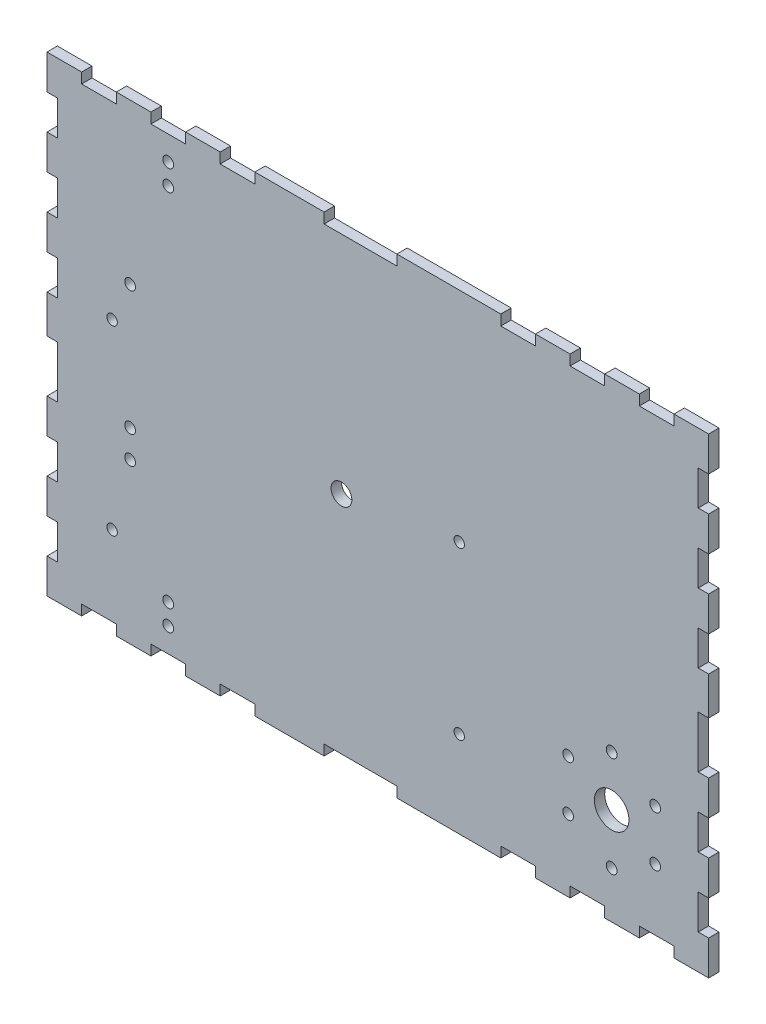
SolidWorks part; units mm, degrees
ref_plane "Front Plane" through (0, 0, 0) normal (0, 0, 1) x (1, 0, 0)
ref_plane "Top Plane" through (0, 0, 0) normal (0, 1, 0) x (1, 0, 0)
ref_plane "Right Plane" through (0, 0, 0) normal (1, 0, 0) x (0, 0, -1)
sketch "Sketch2" plane through (0, 0, 0) normal (0, 0, 1) x (1, 0, 0)
  line L1 (0, 0) -> (191, 0)
  line L2 (0, 0) -> (0, 136)
  line L3 (0, 136) -> (191, 136)
  line L4 (191, 0) -> (191, 136)
  circle A0 centre (35, 16) radius 1.55 construction
  circle A1 centre (35, 10) radius 1.55 construction
  circle A2 centre (24, 46.0692) radius 1.55 construction
  circle A3 centre (24, 54.0692) radius 1.55 construction
  circle A5 centre (24, 89.9308) radius 1.55 construction
  circle A6 centre (35, 120) radius 1.55 construction
  circle A7 centre (35, 126) radius 1.55 construction
  circle A8 centre (175.5574, 35.25) radius 1.55 construction
  circle A9 centre (163, 42.5) radius 1.55 construction
  circle A10 centre (150.4426, 35.25) radius 1.55 construction
  circle A11 centre (150.4426, 20.75) radius 1.55 construction
  circle A12 centre (163, 13.5) radius 1.55 construction
  circle A13 centre (175.5574, 20.75) radius 1.55 construction
  circle A14 centre (35, 16) radius 1.55
  circle A15 centre (35, 10) radius 1.55
  circle A16 centre (24, 46.0692) radius 1.55
  circle A17 centre (24, 54.0692) radius 1.55
  circle A18 centre (18.8, 26) radius 1.5 construction
  circle A19 centre (24, 89.9308) radius 1.55
  circle A20 centre (35, 120) radius 1.55
  circle A21 centre (35, 126) radius 1.55
  circle A22 centre (175.5574, 35.25) radius 1.55
  circle A23 centre (163, 42.5) radius 1.55
  circle A24 centre (150.4426, 35.25) radius 1.55
  circle A25 centre (150.4426, 20.75) radius 1.55
  circle A26 centre (163, 13.5) radius 1.55
  circle A27 centre (175.5574, 20.75) radius 1.55
  circle A28 centre (18.8, 78.5) radius 1.5 construction
  circle A29 centre (18.8, 78.5) radius 1.5
  circle A30 centre (119, 73) radius 1.5 construction
  circle A31 centre (119, 25) radius 1.5 construction
  circle A32 centre (18.8, 26) radius 1.5
  circle A33 centre (119, 73) radius 1.5
  circle A34 centre (119, 25) radius 1.5
extrude "Boss-Extrude1" add sketch "Sketch2" along normal blind 3
ref_axis "Axis1" through (0, 68, 3) along (1, 0, 0)
ref_plane "Plane1" through (0, 68, 0) normal (0, 1, 0) x (1, 0, 0)
ref_axis "Axis2" through (95.5, 0, 3) along (0, 1, 0)
ref_plane "Plane2" through (95.5, 0, 0) normal (1, 0, 0) x (0, 0, -1)
sketch "Sketch3" plane through (0, 0, 3) normal (0, 0, 1) x (1, 0, 0)
  line L0 (0, 3) -> (191, 3) construction
  line L1 (0, 136) -> (0, 0) construction
  line L2 (191, 0) -> (191, 136) construction
  line L3 (0, 0) -> (191, 0) construction
  line L4 (10, 0) -> (10, 3)
  line L5 (20, 0) -> (20, 3)
  line L6 (30, 0) -> (30, 3)
  line L7 (40, 0) -> (40, 3)
  line L8 (50, 0) -> (50, 3)
  line L9 (60, 0) -> (60, 3)
  line L10 (10, 0) -> (20, 0)
  line L11 (20, 3) -> (10, 3)
  line L12 (30, 0) -> (40, 0)
  line L13 (40, 3) -> (30, 3)
  line L14 (50, 0) -> (60, 0)
  line L15 (80, 3) -> (80, 0)
  line L16 (60, 3) -> (50, 3)
  line L17 (181, 0) -> (181, 3)
  line L18 (171, 0) -> (171, 3)
  line L19 (161, 0) -> (161, 3)
  line L20 (151, 0) -> (151, 3)
  line L21 (141, 0) -> (141, 3)
  line L22 (131, 0) -> (131, 3)
  line L23 (181, 0) -> (171, 0)
  line L24 (171, 0) -> (170.9794, -0.0476)
  line L25 (171, 3) -> (181, 3)
  line L26 (181, 3) -> (181.0353, 3.2173)
  line L27 (161, 0) -> (151, 0)
  line L28 (161, 3) -> (151, 3)
  line L29 (141, 0) -> (131, 0)
  line L30 (131, 3) -> (141, 3)
  line L31 (141, 3) -> (140.9859, 2.9583)
  line L32 (101, 0) -> (101, 3)
  line L33 (80, 0) -> (101, 0)
  line L34 (101, 3) -> (80, 3)
  line M15 (0, 0) -> (191, 0)
  dimension "D6" = 20
  dimension "D1" = 3
  dimension "D2" = 10
  dimension "D4" = 10
  dimension "D7" = 30
  dimension "D3" = 6
  dimension "D5" = 6
extrude "Cut-Extrude1" cut sketch "Sketch3" against normal up to next contours L5 L11 L4 M15 | L7 L13 L6 M15 | L9 L16 L8 M15 | L32 L34 L15 M15 | L30 L22 L21 M15 | L19 L28 L20 M15 | L25 L18 L17 M15 region at (176, 1.5, 3) region at (156, 1.5, 3) region at (136, 1.5, 3) region at (90.5, 1.5, 3) region at (55, 1.5, 3) region at (35, 1.5, 3) region at (15, 1.5, 3)
mirror "Mirror1" about plane through (0, 68, 0) normal (0, 1, 0) of "Cut-Extrude1"
sketch "Sketch4" plane through (0, 0, 3) normal (0, 0, 1) x (1, 0, 0)
  line L0 (3, 136) -> (3, 0) construction
  line L1 (10, 136) -> (0, 136) construction
  line L2 (0, 0) -> (10, 0) construction
  line L3 (0, 136) -> (0, 0) construction
  line L4 (0, 126) -> (3, 126)
  line L5 (0, 116) -> (3, 116)
  line L6 (0, 106) -> (3, 106)
  line L7 (0, 96) -> (3, 96)
  line L8 (0, 86) -> (3, 86)
  line L9 (0, 10) -> (3, 10)
  line L10 (0, 20) -> (3, 20)
  line L11 (0, 30) -> (3, 30)
  line L12 (0, 40) -> (3, 40)
  line L13 (0, 50) -> (3, 50)
  line L14 (0, 126) -> (0, 116)
  line L15 (3, 116) -> (3, 126)
  line L16 (0, 106) -> (0, 96)
  line L17 (3, 96) -> (3, 106)
  line L18 (0, 20) -> (0, 10)
  line L19 (3, 10) -> (3, 20)
  line L20 (0, 30) -> (0, 40)
  line L21 (3, 30) -> (3, 40)
  line L22 (0, 65) -> (3, 65)
  line L23 (0, 76) -> (3, 76)
  line L24 (0, 86) -> (0, 76)
  line L25 (3, 76) -> (3, 86)
  line L26 (0, 65) -> (0, 50)
  line L27 (3, 50) -> (3, 65)
  dimension "D1" = 3
  dimension "D2" = 10
  dimension "D4" = 10
  dimension "D6" = 15
  dimension "D3" = 6
  dimension "D5" = 5
extrude "Cut-Extrude2" cut sketch "Sketch4" against normal up to next
mirror "Mirror2" about plane through (95.5, 0, 0) normal (1, 0, 0) of "Cut-Extrude2"
sketch "Sketch6" plane through (0, 0, 3) normal (0, 0, 1) x (1, 0, 0)
  line L0 (116, 0) -> (116, 136) construction
  line L1 (101, 0) -> (131, 0) construction
  line L2 (131, 136) -> (101, 136) construction
  line L3 (191, 68) -> (85, 68) construction
  line L4 (191, 65) -> (191, 76) construction
  dimension "D1" = 106
ref_point "MountPoint-Dif"
sketch "Sketch8" plane through (0, 0, 0) normal (0, 0, -1) x (-1, 0, 0)
  circle A0 centre (-163, 28) radius 8 construction
  circle A1 centre (-163, 28) radius 8
  circle A2 centre (-163, 28) radius 5
  dimension "D1" = 10
extrude "Cut-Extrude3" cut sketch "Sketch8" against normal up to next contours A2 region at (163, 28, 0)
sketch "Sketch9" plane through (0, 0, 3) normal (0, 0, 1) x (1, 0, 0)
  circle A0 centre (85, 68) radius 3
  point P0 (85, 68)
  dimension "D1" = 6
extrude "Cut-Extrude4" cut sketch "Sketch9" against normal up to next
